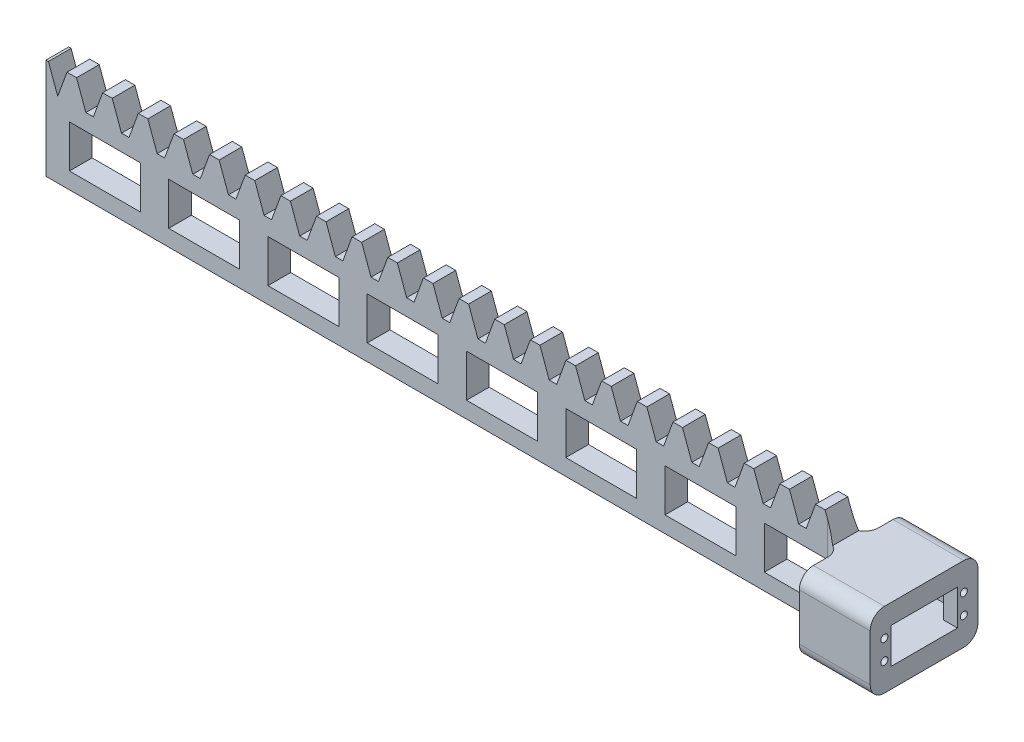
SolidWorks part; units mm, degrees
ref_plane "前视基准面" through (0, 0, 0) normal (0, 0, 1) x (1, 0, 0)
ref_plane "上视基准面" through (0, 0, 0) normal (0, 1, 0) x (1, 0, 0)
ref_plane "右视基准面" through (0, 0, 0) normal (1, 0, 0) x (0, 0, -1)
sketch "草图1" plane through (0, 0, 0) normal (0, 0, 1) x (1, 0, 0)
  line L1 (0, 0) -> (213.6283, 0)
  line L2 (0, 0) -> (0, -10)
  line L3 (0, -10) -> (213.6283, -10)
  line L4 (213.6283, 0) -> (213.6283, -10)
  dimension "D1" = 10
  dimension "L" = 213.6283
extrude "拉伸1" add sketch "草图1" along normal blind 30
sketch "草图2" plane through (0, 0, 30) normal (0, 0, 1) x (1, 0, 0)
  line L0 (0, 0) -> (3.2757, 9)
  line L1 (3.2757, 9) -> (6.6472, 9)
  line L2 (6.6472, 9) -> (9.9229, 0)
  line L3 (213.6283, 0) -> (0, 0) construction
  line L4 (0, 0) -> (9.9229, 0)
  line L5 (1.8199, 5) -> (8.103, 5) construction
  dimension "D2" = 70
  dimension "alpha" = 110
  dimension "ha" = 4
  dimension "hf" = 5
  dimension "S" = 6.2832
extrude "拉伸2" add sketch "草图2" against normal up to surface (30 mm away) up to face at (106.8142, -5, 0)
pattern_linear "阵列(线性)1" count 17 spacing 12.5664 along (1, 0, 0) of "拉伸2"
sketch "草图3" plane through (0, 0, 30) normal (0, 0, 1) x (1, 0, 0)
  line L71 (0, 0) -> (0, -10)
  line L72 (0, -10) -> (213.6283, -10)
  line L73 (213.6283, -10) -> (213.6283, 0)
  line L74 (213.6283, 0) -> (210.9848, 0)
  line L75 (210.9848, 0) -> (207.7091, 9)
  line L76 (207.7091, 9) -> (204.3377, 9)
  line L77 (204.3377, 9) -> (201.0619, 0)
  line L78 (201.0619, 0) -> (198.4184, 0)
  line L79 (198.4184, 0) -> (195.1427, 9)
  line L80 (195.1427, 9) -> (191.7713, 9)
  line L81 (191.7713, 9) -> (188.4956, 0)
  line L82 (188.4956, 0) -> (185.8521, 0)
  line L83 (185.8521, 0) -> (182.5763, 9)
  line L84 (182.5763, 9) -> (179.2049, 9)
  line L85 (179.2049, 9) -> (175.9292, 0)
  line L86 (175.9292, 0) -> (173.2857, 0)
  line L87 (173.2857, 0) -> (170.01, 9)
  line L88 (170.01, 9) -> (166.6386, 9)
  line L89 (166.6386, 9) -> (163.3628, 0)
  line L90 (163.3628, 0) -> (160.7193, 0)
  line L91 (160.7193, 0) -> (157.4436, 9)
  line L92 (157.4436, 9) -> (154.0722, 9)
  line L93 (154.0722, 9) -> (150.7964, 0)
  line L94 (150.7964, 0) -> (148.153, 0)
  line L95 (148.153, 0) -> (144.8772, 9)
  line L96 (144.8772, 9) -> (141.5058, 9)
  line L97 (141.5058, 9) -> (138.2301, 0)
  line L98 (138.2301, 0) -> (135.5866, 0)
  line L99 (135.5866, 0) -> (132.3109, 9)
  line L100 (132.3109, 9) -> (128.9394, 9)
  line L101 (128.9394, 9) -> (125.6637, 0)
  line L102 (125.6637, 0) -> (123.0202, 0)
  line L103 (123.0202, 0) -> (119.7445, 9)
  line L104 (119.7445, 9) -> (116.3731, 9)
  line L105 (116.3731, 9) -> (113.0973, 0)
  line L106 (113.0973, 0) -> (110.4539, 0)
  line L107 (110.4539, 0) -> (107.1781, 9)
  line L108 (107.1781, 9) -> (103.8067, 9)
  line L109 (103.8067, 9) -> (100.531, 0)
  line L110 (100.531, 0) -> (97.8875, 0)
  line L111 (97.8875, 0) -> (94.6117, 9)
  line L112 (94.6117, 9) -> (91.2403, 9)
  line L113 (91.2403, 9) -> (87.9646, 0)
  line L114 (87.9646, 0) -> (85.3211, 0)
  line L115 (85.3211, 0) -> (82.0454, 9)
  line L116 (82.0454, 9) -> (78.674, 9)
  line L117 (78.674, 9) -> (75.3982, 0)
  line L118 (75.3982, 0) -> (72.7547, 0)
  line L119 (72.7547, 0) -> (69.479, 9)
  line L120 (69.479, 9) -> (66.1076, 9)
  line L121 (66.1076, 9) -> (62.8319, 0)
  line L122 (62.8319, 0) -> (60.1884, 0)
  line L123 (60.1884, 0) -> (56.9126, 9)
  line L124 (56.9126, 9) -> (53.5412, 9)
  line L125 (53.5412, 9) -> (50.2655, 0)
  line L126 (50.2655, 0) -> (47.622, 0)
  line L127 (47.622, 0) -> (44.3463, 9)
  line L128 (44.3463, 9) -> (40.9748, 9)
  line L129 (40.9748, 9) -> (37.6991, 0)
  line L130 (37.6991, 0) -> (35.0556, 0)
  line L131 (35.0556, 0) -> (31.7799, 9)
  line L132 (31.7799, 9) -> (28.4085, 9)
  line L133 (28.4085, 9) -> (25.1327, 0)
  line L134 (25.1327, 0) -> (22.4893, 0)
  line L135 (22.4893, 0) -> (19.2135, 9)
  line L136 (19.2135, 9) -> (15.8421, 9)
  line L137 (15.8421, 9) -> (12.5664, 0)
  line L138 (12.5664, 0) -> (9.9229, 0)
  line L139 (9.9229, 0) -> (6.6472, 9)
  line L140 (6.6472, 9) -> (3.2757, 9)
  line L141 (3.2757, 9) -> (0, 0)
  line L142 (0, 0) -> (0, -10)
  line L143 (0, -10) -> (213.6283, -10)
  line L144 (213.6283, -10) -> (213.6283, 0)
  line L145 (213.6283, 0) -> (210.9848, 0)
  line L146 (210.9848, 0) -> (207.7091, 9)
  line L147 (207.7091, 9) -> (204.3377, 9)
  line L148 (204.3377, 9) -> (201.0619, 0)
  line L149 (201.0619, 0) -> (198.4184, 0)
  line L150 (198.4184, 0) -> (195.1427, 9)
  line L151 (195.1427, 9) -> (191.7713, 9)
  line L152 (191.7713, 9) -> (188.4956, 0)
  line L153 (188.4956, 0) -> (185.8521, 0)
  line L154 (185.8521, 0) -> (182.5763, 9)
  line L155 (182.5763, 9) -> (179.2049, 9)
  line L156 (179.2049, 9) -> (175.9292, 0)
  line L157 (175.9292, 0) -> (173.2857, 0)
  line L158 (173.2857, 0) -> (170.01, 9)
  line L159 (170.01, 9) -> (166.6386, 9)
  line L160 (166.6386, 9) -> (163.3628, 0)
  line L161 (163.3628, 0) -> (160.7193, 0)
  line L162 (160.7193, 0) -> (157.4436, 9)
  line L163 (157.4436, 9) -> (154.0722, 9)
  line L164 (154.0722, 9) -> (150.7964, 0)
  line L165 (150.7964, 0) -> (148.153, 0)
  line L166 (148.153, 0) -> (144.8772, 9)
  line L167 (144.8772, 9) -> (141.5058, 9)
  line L168 (141.5058, 9) -> (138.2301, 0)
  line L169 (138.2301, 0) -> (135.5866, 0)
  line L170 (135.5866, 0) -> (132.3109, 9)
  line L171 (132.3109, 9) -> (128.9394, 9)
  line L172 (128.9394, 9) -> (125.6637, 0)
  line L173 (125.6637, 0) -> (123.0202, 0)
  line L174 (123.0202, 0) -> (119.7445, 9)
  line L175 (119.7445, 9) -> (116.3731, 9)
  line L176 (116.3731, 9) -> (113.0973, 0)
  line L177 (113.0973, 0) -> (110.4539, 0)
  line L178 (110.4539, 0) -> (107.1781, 9)
  line L179 (107.1781, 9) -> (103.8067, 9)
  line L180 (103.8067, 9) -> (100.531, 0)
  line L181 (100.531, 0) -> (97.8875, 0)
  line L182 (97.8875, 0) -> (94.6117, 9)
  line L183 (94.6117, 9) -> (91.2403, 9)
  line L184 (91.2403, 9) -> (87.9646, 0)
  line L185 (87.9646, 0) -> (85.3211, 0)
  line L186 (85.3211, 0) -> (82.0454, 9)
  line L187 (82.0454, 9) -> (78.674, 9)
  line L188 (78.674, 9) -> (75.3982, 0)
  line L189 (75.3982, 0) -> (72.7547, 0)
  line L190 (72.7547, 0) -> (69.479, 9)
  line L191 (69.479, 9) -> (66.1076, 9)
  line L192 (66.1076, 9) -> (62.8319, 0)
  line L193 (62.8319, 0) -> (60.1884, 0)
  line L194 (60.1884, 0) -> (56.9126, 9)
  line L195 (56.9126, 9) -> (53.5412, 9)
  line L196 (53.5412, 9) -> (50.2655, 0)
  line L197 (50.2655, 0) -> (47.622, 0)
  line L198 (47.622, 0) -> (44.3463, 9)
  line L199 (44.3463, 9) -> (40.9748, 9)
  line L200 (40.9748, 9) -> (37.6991, 0)
  line L201 (37.6991, 0) -> (35.0556, 0)
  line L202 (35.0556, 0) -> (31.7799, 9)
  line L203 (31.7799, 9) -> (28.4085, 9)
  line L204 (28.4085, 9) -> (25.1327, 0)
  line L205 (25.1327, 0) -> (22.4893, 0)
  line L206 (22.4893, 0) -> (19.2135, 9)
  line L207 (19.2135, 9) -> (15.8421, 9)
  line L208 (15.8421, 9) -> (12.5664, 0)
  line L209 (12.5664, 0) -> (9.9229, 0)
  line L210 (9.9229, 0) -> (6.6472, 9)
  line L211 (6.6472, 9) -> (3.2757, 9)
  line L212 (3.2757, 9) -> (0, 0)
  dimension "D1" = 0
extrude "切除-拉伸1" cut sketch "草图3" against normal blind 10
sketch "草图4" plane through (0, 0, 0) normal (-1, 0, 0) x (0, 0, 1)
  line L5 (0, 9) -> (20, 9) construction
  line L6 (0, -10) -> (12, -10)
  line L7 (0, -10) -> (0, 9)
  line L8 (0, 9) -> (12, 9)
  line L9 (12, -10) -> (12, 9)
  line L10 (20, -10) -> (0, -10) construction
  dimension "D1" = 12
extrude "切除-拉伸3" cut sketch "草图4" against normal through all
sketch "草图5" plane through (0, 0, 0) normal (-1, 0, 0) x (0, 0, 1)
  line L1 (20, -10) -> (12, -10)
  line L2 (20, -10) -> (20, -26.5)
  line L3 (20, -26.5) -> (12, -26.5)
  line L4 (12, -10) -> (12, -26.5)
  dimension "D1" = 16.5
extrude "凸台-拉伸1" add sketch "草图5" against normal up to surface (213.6283 mm away) up to face at (213.6283, -5, 16)
sketch "草图16" plane through (0, 0, 12) normal (0, 0, -1) x (-1, 0, 0)
  line L0 (-6.6472, 9) -> (-3.2757, 9) construction
  line L1 (-4.9614, 9) -> (0, 9)
  line L2 (-4.9614, 9) -> (-4.9614, -26.5)
  line L3 (-4.9614, -26.5) -> (0, -26.5)
  line L4 (0, 9) -> (0, -26.5)
extrude "切除-拉伸12" cut sketch "草图16" against normal up to next
mirror "镜向1" about plane through (4.9614, 9, 20.001) normal (1, 0, 0) of bodies 119 107
sketch "草图8" plane through (213.6283, 0, 0) normal (1, 0, 0) x (0, 0, -1)
  line L12 (-20, -26.5) -> (-12, -26.5) construction
  line L17 (-35, 0) -> (3, 0)
  line L18 (-35, 0) -> (-35, -26.5)
  line L19 (-35, -26.5) -> (3, -26.5)
  line L20 (3, 0) -> (3, -26.5)
  line L21 (-16, 0) -> (-16, -35.0155) construction
  line L22 (-35, -13.25) -> (-36.7635, -13.25) construction
  line L23 (-20, -13.25) -> (-22.7118, -13.25) construction
  line L24 (-20, -26.5) -> (-20, 0) construction
  circle A0 centre (-30, -16.75) radius 1.25
  circle A1 centre (-30, -9.75) radius 1.25
  circle A4 centre (-2, -9.75) radius 1.25
  circle A5 centre (-2, -16.75) radius 1.25
  point P3 (-16, -26.5)
  dimension "D3" = 2.5
  dimension "D1" = 28
  dimension "D2" = 7
  dimension "D4" = 5
  dimension "D5" = 9.75
  dimension "D6" = 5
  dimension "D7" = 9.75
extrude "凸台-拉伸2" add sketch "草图8" along normal blind 25
sketch "草图9" plane through (0, 0, 20) normal (0, 0, 1) x (1, 0, 0)
  line L2 (-203.7054, -13.25) -> (-193.7708, -13.25) construction
  line L3 (-198.7054, -5.75) -> (-173.7054, -5.75)
  line L4 (-198.7054, -5.75) -> (-198.7054, -20.75)
  line L5 (-198.7054, -20.75) -> (-173.7054, -20.75)
  line L6 (-173.7054, -5.75) -> (-173.7054, -20.75)
  line L7 (-203.7054, -26.5) -> (-203.7054, 0) construction
  line L8 (-198.7054, -13.25) -> (-48.169, -13.25) construction
  line L9 (-163.7054, -5.75) -> (-163.7054, -20.75)
  line L10 (-163.7054, -5.75) -> (-138.7054, -5.75)
  line L11 (-138.7054, -5.75) -> (-138.7054, -20.75)
  line L12 (-163.7054, -20.75) -> (-138.7054, -20.75)
  line L13 (-128.7054, -5.75) -> (-128.7054, -20.75)
  line L14 (-128.7054, -5.75) -> (-103.7054, -5.75)
  line L15 (-103.7054, -5.75) -> (-103.7054, -20.75)
  line L16 (-128.7054, -20.75) -> (-103.7054, -20.75)
  line L17 (-93.7054, -5.75) -> (-93.7054, -20.75)
  line L18 (-93.7054, -5.75) -> (-68.7054, -5.75)
  line L19 (-68.7054, -5.75) -> (-68.7054, -20.75)
  line L20 (-93.7054, -20.75) -> (-68.7054, -20.75)
  line L21 (-58.7054, -5.75) -> (-58.7054, -20.75)
  line L22 (-58.7054, -5.75) -> (-33.7054, -5.75)
  line L23 (-33.7054, -5.75) -> (-33.7054, -20.75)
  line L24 (-58.7054, -20.75) -> (-33.7054, -20.75)
  line L25 (-23.7054, -5.75) -> (-23.7054, -20.75)
  line L26 (-23.7054, -5.75) -> (1.2946, -5.75)
  line L27 (1.2946, -5.75) -> (1.2946, -20.75)
  line L28 (-23.7054, -20.75) -> (1.2946, -20.75)
  line L29 (11.2946, -5.75) -> (11.2946, -20.75)
  line L30 (11.2946, -5.75) -> (36.2946, -5.75)
  line L31 (36.2946, -5.75) -> (36.2946, -20.75)
  line L32 (11.2946, -20.75) -> (36.2946, -20.75)
  line L33 (46.2946, -5.75) -> (46.2946, -20.75)
  line L34 (46.2946, -5.75) -> (71.2946, -5.75)
  line L35 (71.2946, -5.75) -> (71.2946, -20.75)
  line L36 (46.2946, -20.75) -> (71.2946, -20.75)
  line L37 (81.2946, -5.75) -> (81.2946, -20.75)
  line L38 (81.2946, -5.75) -> (106.2946, -5.75)
  line L39 (106.2946, -5.75) -> (106.2946, -20.75)
  line L40 (81.2946, -20.75) -> (106.2946, -20.75)
  line L41 (116.2946, -5.75) -> (116.2946, -20.75)
  line L42 (116.2946, -5.75) -> (141.2946, -5.75)
  line L43 (141.2946, -5.75) -> (141.2946, -20.75)
  line L44 (116.2946, -20.75) -> (141.2946, -20.75)
  line L45 (151.2946, -5.75) -> (151.2946, -20.75)
  line L46 (151.2946, -5.75) -> (176.2946, -5.75)
  line L47 (176.2946, -5.75) -> (176.2946, -20.75)
  line L48 (151.2946, -20.75) -> (176.2946, -20.75)
  line L49 (186.2946, -5.75) -> (186.2946, -20.75)
  line L50 (186.2946, -5.75) -> (211.2946, -5.75)
  line L51 (211.2946, -5.75) -> (211.2946, -20.75)
  line L52 (186.2946, -20.75) -> (211.2946, -20.75)
  dimension "D1" = 15
  dimension "D2" = 25
  dimension "D3" = 5
  dimension "D4" = 12
extrude "切除-拉伸4" cut sketch "草图9" against normal up to next
sketch "草图10" plane through (0, 0, 20) normal (0, 0, 1) x (1, 0, 0)
  line L0 (213.6283, -26.5) -> (213.6283, 0) construction
  line L1 (211.2946, -20.75) -> (213.6283, -20.75)
  line L2 (211.2946, -20.75) -> (211.2946, -5.75)
  line L3 (211.2946, -5.75) -> (213.6283, -5.75)
  line L4 (213.6283, -20.75) -> (213.6283, -5.75)
  line L5 (211.2946, -5.75) -> (186.2946, -5.75) construction
extrude "切除-拉伸5" cut sketch "草图10" against normal up to next
sketch "草图11" plane through (213.6283, 0, 0) normal (-1, 0, 0) x (0, 0, 1)
  line L0 (-1, -13.25) -> (2.6927, -13.25) construction
  line L1 (-1, -7) -> (33, -7)
  line L2 (-1, -7) -> (-1, -19.5)
  line L3 (-1, -19.5) -> (33, -19.5)
  line L4 (33, -7) -> (33, -19.5)
  line L5 (16, -7) -> (16, -11.2777) construction
  line L6 (2, -9.75) -> (30, -9.75) construction
  line L7 (2, -9.75) -> (2, -16.75) construction
  line L8 (2, -13.25) -> (2.5136, -13.25) construction
  line L9 (16, -9.75) -> (16, -12.4847) construction
  dimension "D1" = 12.5
  dimension "D2" = 34
extrude "切除-拉伸6" cut sketch "草图11" against normal blind 20
sketch "草图12" plane through (238.6283, 0, 0) normal (1, 0, 0) x (0, 0, -1)
  line L0 (-30, -9.75) -> (-2, -16.75) construction
  line L1 (-2, -9.75) -> (-30, -16.75) construction
  line L3 (-27.75, -19.5) -> (-4.25, -19.5)
  line L4 (-27.75, -19.5) -> (-27.75, -7)
  line L5 (-27.75, -7) -> (-4.25, -7)
  line L6 (-4.25, -19.5) -> (-4.25, -7)
  line L7 (-27.75, -19.5) -> (-4.25, -7) construction
  line L8 (-27.75, -7) -> (-4.25, -19.5) construction
  point P8 (-16, -13.25)
  point P9 (-16, -13.25)
  dimension "D1" = 12.5
  dimension "D2" = 23.5
extrude "切除-拉伸7" cut sketch "草图12" against normal up to next
fillet "圆角1" radius 5 4 edges at (226.1283, -26.5, 35) (226.1283, 0, 35) (226.1283, -26.5, -3) (226.1283, 0, -3)
fillet "圆角2" radius 5 6 edges at (213.6283, -2.875, 12) (213.6283, -23.625, 12) (213.6283, -23.625, 20) (213.6283, -2.875, 20) (213.6283, -5.75, 16) (213.6283, -20.75, 16)
sketch "草图13" plane through (0, 0, 20) normal (0, 0, 1) x (1, 0, 0)
  line L1 (-203.7054, -26.5) -> (-62.8319, -26.5)
  line L2 (-203.7054, -26.5) -> (-203.7054, 9)
  line L3 (-203.7054, 9) -> (-62.8319, 9)
  line L4 (-62.8319, -26.5) -> (-62.8319, 9)
  line L5 (-84.6889, 9) -> (-81.3174, 9) construction
extrude "切除-拉伸8" cut sketch "草图13" against normal up to next
mirror "镜向3" about plane through (-62.8319, -26.5, -3.001) normal (1, 0, 0) of bodies 114
sketch "草图17" plane through (0, 0, -3) normal (0, 0, -1) x (-1, 0, 0)
  line L0 (66.9583, -20.75) -> (66.9583, -5.75) construction
  line L1 (66.9583, 12.1619) -> (373.1564, 12.1619)
  line L2 (66.9583, 12.1619) -> (66.9583, -38.7901)
  line L3 (66.9583, -38.7901) -> (373.1564, -38.7901)
  line L4 (373.1564, 12.1619) -> (373.1564, -38.7901)
extrude "切除-拉伸13" cut sketch "草图17" against normal up to next
equation "\"d\"=\"S@草图2\" * 2"
equation "\"z\"= int(  \"L@草图1\" / (  \"S@草图2\" * 2 ) + 0.5 )"
